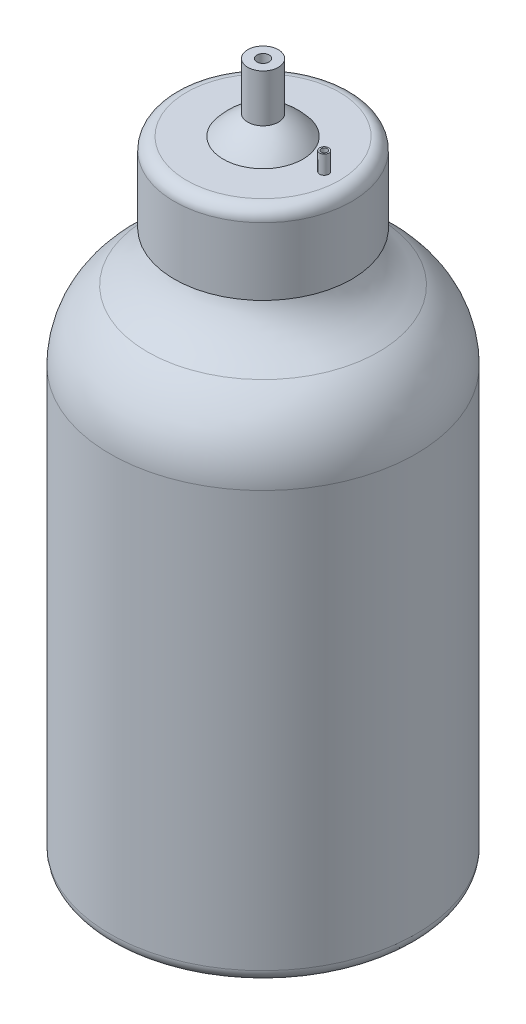
SolidWorks part; units mm, degrees
ref_plane "Front Plane" through (0, 0, 0) normal (0, 0, 1) x (1, 0, 0)
ref_plane "Top Plane" through (0, 0, 0) normal (0, 1, 0) x (1, 0, 0)
ref_plane "Right Plane" through (0, 0, 0) normal (1, 0, 0) x (0, 0, -1)
sketch "Sketch1" plane through (0, 0, 0) normal (0, 0, 1) x (1, 0, 0)
  line L0 (0, 0) -> (25, 0)
  line L1 (25, 0) -> (25, 70)
  line L2 (0, 0) -> (0, 81.4068) construction
  line L3 (0, 90) -> (12, 90)
  line L4 (0, 0) -> (0, 90)
  arc A0 (25, 70) -> (18.9034, 81.4068) centre (11.2805, 70) ccw
  spline S0 degree 3 poles (12, 90) (12, 88.1839) (13.886, 84.4588) (17.4312, 82.3907) (18.9034, 81.4068) knots 0 0 0 0 0.322483 0.670614 0.670614 0.670614 0.670614
  point P10 (19.5225, 87.8846)
  point P11 (24.0377, 77.698)
  point P12 (13.714, 88.9727)
  point P13 (17.4173, 83.5177)
  point P14 (14.9651, 86.1201)
  point P15 (14.1975, 84.9844)
  point P16 (18.9034, 81.4068)
  dimension "D1" = 25
  dimension "D3" = 12
  dimension "D4" = 90
  dimension "D5" = 70
revolve "Revolve1" add sketch "Sketch1" angle 360 about L2
fillet "Fillet1" radius 2 1 edges at (0, 0, -25)
shell "Shell1" thickness 1 removed face at (0, 90, -12)
sketch "Sketch3" plane through (0, 90, 0) normal (0, 1, 0) x (1, 0, 0)
  circle A1 centre (0, 0) radius 12
  circle A2 centre (0, 0) radius 12
  dimension "D1" = 0
extrude "Extrude-Thin1" add sketch "Sketch3" along normal blind 10 thin thin type one direction reverse wall 1
sketch "Sketch4" plane through (0, 0, 0) normal (0, 0, 1) x (1, 0, 0)
  line L0 (-13, 89.5) -> (-13, 101)
  line L1 (-13, 101) -> (-2.5, 101)
  line L2 (-13, 89.5) -> (-14.5, 89.5)
  line L3 (-14.5, 89.5) -> (-14.5, 102.5)
  line L4 (-14.5, 102.5) -> (-6.5, 102.5)
  line L5 (-2.5, 105.743) -> (-2.5, 113.5215)
  line L6 (-2.5, 113.5215) -> (-1, 113.5215)
  line L7 (-1, 113.5215) -> (-1, 101)
  line L8 (0, 100) -> (0, 118.647) construction
  line L9 (12, 100) -> (-12, 100) construction
  line L10 (11, 100) -> (-11, 100) construction
  line L11 (-2.5, 101) -> (-2.5, 11)
  line L12 (-1, 101) -> (-1, 11)
  line L13 (-1, 11) -> (-2.5, 11)
  spline S0 degree 2 poles (-6.5, 102.5) (-4.835, 104.5417) (-2.5, 105.743) knots 0 0 0 1 1 1
  dimension "D1" = 2
  dimension "D2" = 12
  dimension "D3" = 11.5
  dimension "D4" = 13
  dimension "D5" = 1.5
  dimension "D6" = 8
  dimension "D7" = 1.5
  dimension "D8" = 1.5
  dimension "D9" = 1
  dimension "D10" = 14.5
  dimension "D11" = 5
  dimension "D12" = 90
revolve "Revolve2" add sketch "Sketch4" angle 360 about L8
fillet "Fillet2" radius 2 1 edges at (14.5, 102.5, 0)
sketch "Sketch5" plane through (0, 102.5, 0) normal (0, 1, 0) x (1, 0, 0)
  circle A0 centre (10, 0) radius 0.5
  circle A1 centre (10, 0) radius 0.75
  dimension "D1" = 10
  dimension "D2" = 1.5
  dimension "D3" = 1
extrude "Cut-Extrude1" cut sketch "Sketch5" against normal blind 10 contours A0
extrude "Boss-Extrude1" add sketch "Sketch5<3>" along normal blind 3 contours A0 | A1 region at (10, 102.5, 0)
sketch "Sketch5<3>" plane through (0, 102.5, 0) normal (0, 1, 0) x (1, 0, 0) same geometry as "Sketch5"
